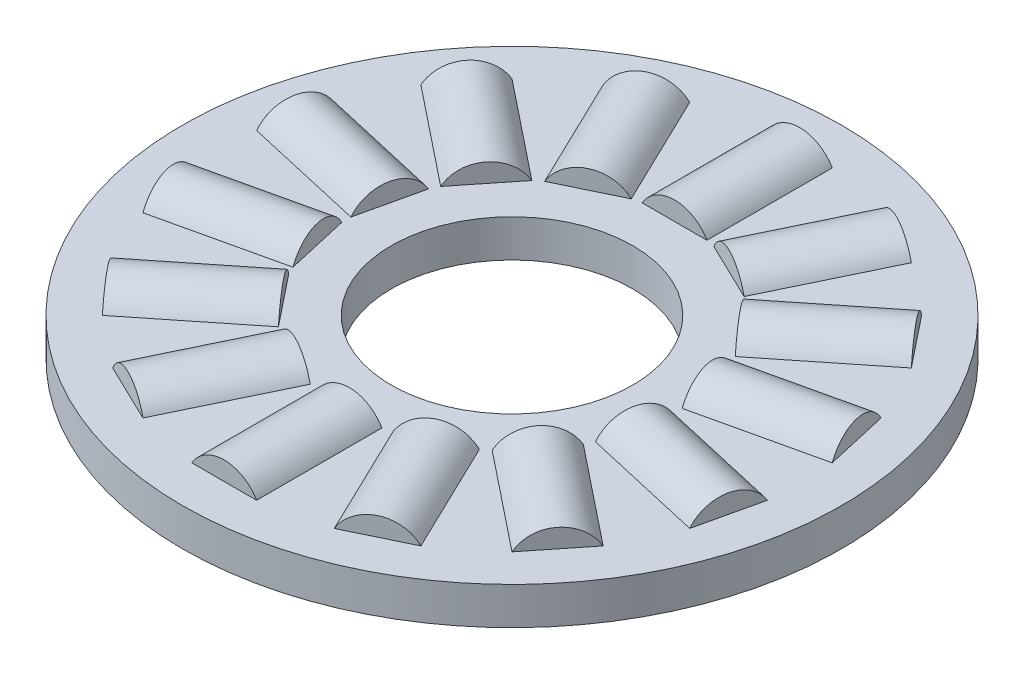
SolidWorks part; units mm, degrees
ref_plane "Front Plane" through (0, 0, 0) normal (0, 0, 1) x (1, 0, 0)
ref_plane "Top Plane" through (0, 0, 0) normal (0, 1, 0) x (1, 0, 0)
ref_plane "Right Plane" through (0, 0, 0) normal (1, 0, 0) x (0, 0, -1)
sketch "Sketch1" plane through (0, 0, 0) normal (1, 0, 0) x (0, 0, -1)
  line L0 (-8.7312, 0) -> (8.7313, 0) construction
  line L1 (0, -0.9922) -> (0, 0.9922) construction
  line L2 (-8.7312, 0.4961) -> (-3.2004, 0.4961)
  line L3 (-8.7312, 0.4961) -> (-8.7312, -0.4961)
  line L4 (-8.7312, -0.4961) -> (-3.2004, -0.4961)
  line L5 (-3.2004, 0.4961) -> (-3.2004, -0.4961)
  line L7 (-5.9658, 0.9922) -> (-5.9658, 0.4961) construction
  line L8 (-7.6251, 0.9922) -> (-4.3066, 0.9922) construction
  line L9 (-7.6251, 0.9922) -> (-7.6251, -0.9922) construction
  line L10 (-7.6251, -0.9922) -> (-4.3066, -0.9922) construction
  line L11 (-4.3066, 0.9922) -> (-4.3066, -0.9922) construction
  line L12 (8.7312, 0.9922) -> (8.7312, -0.9922) construction
  point P16 (-7.6251, 0)
  point P21 (8.7313, 0)
  dimension "OD" = 17.4625
  dimension "ID" = 6.4008
  dimension "Washer Thickness" = 0.9922
  dimension "D1" = 3.3185
  dimension "Thickness" = 1.9844
sketch "Sketch6" plane through (0, 0, 0) normal (0, 1, 0) x (1, 0, 0)
  circle A0 centre (0, 0) radius 8.7313 construction
  circle A1 centre (0, 0) radius 3.2004 construction
  circle A2 centre (0, 0) radius 3.175 construction
  dimension "For Shaft Diameter" = 6.35
  dimension "OD" = 17.4625
  dimension "ID" = 6.4008
sketch "Sketch5" plane through (0, 0, 0) normal (1, 0, 0) x (0, 0, -1)
  line L1 (-8.7312, 0.4961) -> (-3.2004, 0.4961)
  line L2 (-8.7312, 0.4961) -> (-8.7312, -0.4961)
  line L3 (-8.7312, -0.4961) -> (-3.2004, -0.4961)
  line L4 (-3.2004, 0.4961) -> (-3.2004, -0.4961)
revolve "Revolve3" add sketch "Sketch5" angle 360 about L1
sketch "Sketch3" plane through (0, 0, 0) normal (1, 0, 0) x (0, 0, -1)
  line L0 (-7.6251, 0.9922) -> (-7.6251, -0.9922) construction
  line L1 (-7.6251, 0) -> (-4.3066, 0)
  line L2 (-7.6251, 0) -> (-7.6251, 0.9922)
  line L3 (-7.6251, 0.9922) -> (-4.3066, 0.9922)
  line L4 (-4.3066, 0) -> (-4.3066, 0.9922)
revolve "Cut-Revolve1" cut sketch "Sketch3" angle 360 about L1
sketch "Sketch2" plane through (0, 0, 0) normal (1, 0, 0) x (0, 0, -1)
  line L1 (-7.6251, 0) -> (-4.3066, 0)
  line L2 (-7.6251, 0) -> (-7.6251, 0.9922)
  line L3 (-7.6251, 0.9922) -> (-4.3066, 0.9922)
  line L4 (-4.3066, 0) -> (-4.3066, 0.9922)
revolve "Revolve2" add sketch "Sketch2" angle 360 about L1
ref_axis "Axis1" through (0, 0.9922, 0) along (0, -1, 0)
pattern_circular "CirPattern1" count 14 every 25.714 about axis through (0, 0.9922, 0) along (0, -1, 0) of bodies 187 411
pattern_circular "CirPattern2" count 14 every 25.714 about axis through (0, 0.9922, 0) along (0, -1, 0) of "Cut-Revolve1"
equation "\"Rollers@CirPattern1\"= \"OD@Sketch1\" * 20"
equation "\"Angle@CirPattern1\" = 360/\"Rollers@CirPattern1\""
equation "\"D1@CirPattern2\" = \"Rollers@CirPattern1\""
equation "\"D2@CirPattern2\" = \"Angle@CirPattern1\""
equation "\"D1@Sketch1\"=((\"OD@Sketch1\"-\"ID@Sketch1\")/2)*.6"
